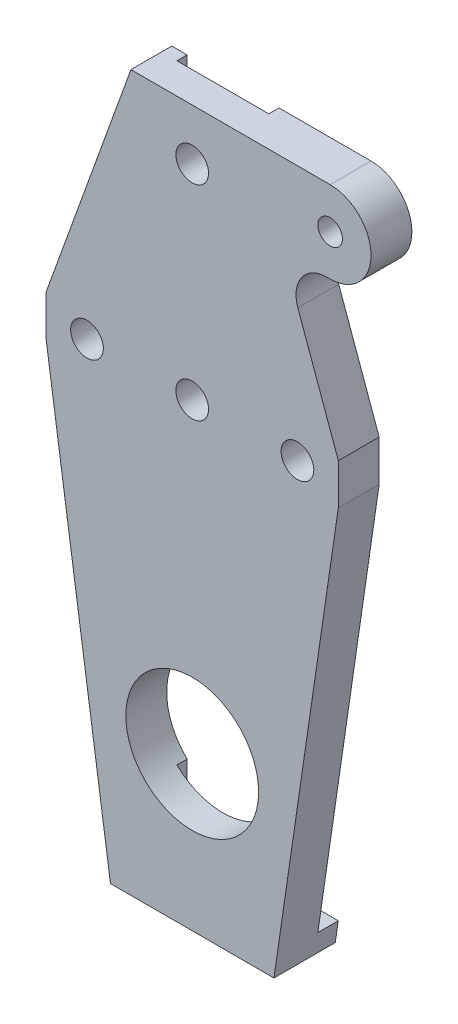
SolidWorks part; units mm, degrees
ref_plane "前视基准面" through (0, 0, 0) normal (0, 0, 1) x (1, 0, 0)
ref_plane "上视基准面" through (0, 0, 0) normal (0, 1, 0) x (1, 0, 0)
ref_plane "右视基准面" through (0, 0, 0) normal (1, 0, 0) x (0, 0, -1)
sketch "Model" plane through (0, 0, 0) normal (0, 0, 1) x (1, 0, 0)
  line L0 (37.0406, 24.4545) -> (36.6995, 24.4545)
  line L1 (33.8777, 20.4362) -> (37.8406, 9.4545)
  line L2 (37.8406, 5.4545) -> (37.8406, 9.4545)
  line L3 (31.5406, -37.5455) -> (37.8406, 5.4545)
  line L4 (28.0406, -35.5455) -> (31.8336, -35.5455)
  line L5 (28.0406, -37.5455) -> (28.0406, -27.2359)
  line L6 (28.0406, -17.855) -> (28.0406, 32.4545)
  line L7 (19.0406, -17.855) -> (19.0406, 32.4545)
  line L8 (19.0406, -37.5455) -> (19.0406, -27.2359)
  line L9 (15.5406, -37.5455) -> (9.2406, 5.4545)
  line L10 (9.2406, 5.4545) -> (9.2406, 9.4545)
  line L11 (17.5406, 32.4545) -> (9.2406, 9.4545)
  line L12 (17.5406, 32.4545) -> (37.0406, 32.4545)
  line L13 (31.5406, -37.5455) -> (15.5406, -37.5455)
  line L14 (19.0406, -35.5455) -> (15.2476, -35.5455)
  circle A0 centre (33.8406, 7.4545) radius 3.245
  circle A1 centre (37.0406, 28.4545) radius 1.2
  arc A2 (36.6995, 24.4545) -> (33.8777, 20.4362) centre (36.6995, 21.4545) ccw
  arc A3 (37.0406, 24.4545) -> (37.0406, 32.4545) centre (37.0406, 28.4545) ccw
  circle A4 centre (23.5406, 27.4545) radius 1.6
  circle A5 centre (23.5406, 7.4545) radius 1.6
  circle A6 centre (13.2406, 7.4545) radius 3.245
  circle A7 centre (23.5406, -22.5455) radius 6.5
  circle A8 centre (13.2406, 7.4545) radius 1.6
  circle A9 centre (33.8406, 7.4545) radius 1.6
extrude "凸台-拉伸4" add sketch "Model" against normal blind 4 contours A7 L7 L12 L11 L10 L9 L14 L8 A6 | A7 L5 L4 L3 L2 L1 A2 L0 A3 L12 L6 A0 A1 | A0 A9 | L13 L3 L4 L5 | L8 L14 L9 L13 | A8 | A6 region at (32.1881, 2.9949, 0) region at (15.4779, -1.6335, 0) region at (29.8648, -36.5321, 0) region at (17.2164, -36.5321, 0) region at (30.6874, 7.4545, 0) region at (13.2406, 7.4545, 0)
extrude "凸台-拉伸5" add sketch "Model<7>" against normal blind 3 contours A7 L8 L13 L5 | A7 L6 L12 L7 A4 A5 region at (27.5295, 7.2998, 0) region at (23.5406, -32.9977, 0)
sketch "Model<7>" plane through (0, 0, 0) normal (0, 0, 1) x (1, 0, 0) same geometry as "Model"
extrude "凸台-拉伸6" add sketch "Model<8>" against normal blind 6 contours L13 L3 L4 L5 | L8 L14 L9 L13 region at (29.8648, -36.5321, 0) region at (17.2164, -36.5321, 0)
sketch "Model<8>" plane through (0, 0, 0) normal (0, 0, 1) x (1, 0, 0) same geometry as "Model"
chamfer "倒角2" distance 1.65 angle 45 2 edges at (14.8406, 7.4545, -4) (35.4406, 7.4545, -4)
